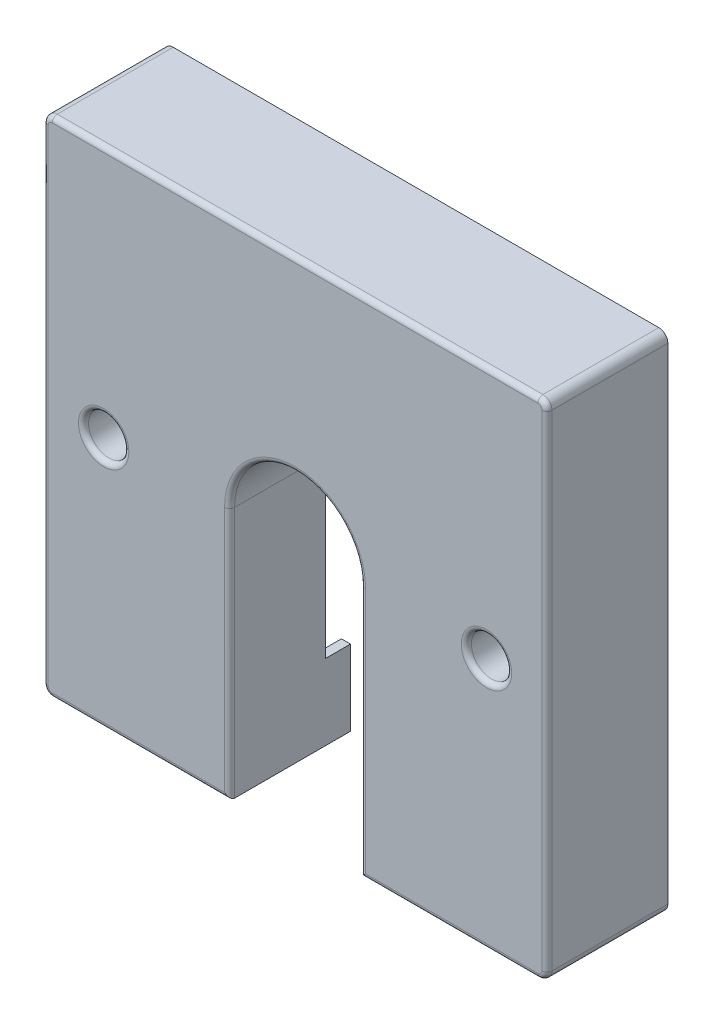
SolidWorks part; units mm, degrees
ref_plane "Front Plane" through (0, 0, 0) normal (0, 0, 1) x (1, 0, 0)
ref_plane "Top Plane" through (0, 0, 0) normal (0, 1, 0) x (1, 0, 0)
ref_plane "Right Plane" through (0, 0, 0) normal (1, 0, 0) x (0, 0, -1)
ref_plane "Plane1" through (0, 0, 121.3011) normal (0, 0, 1) x (1, 0, 0)
sketch "Sketch1" plane through (0, 0, 121.3011) normal (0, 0, 1) x (1, 0, 0)
  line L0 (-25.5449, 99.8167) -> (-25.5449, -0.1833)
  line L1 (-25.5449, -0.1833) -> (74.4551, -0.1833)
  line L2 (74.4551, -0.1833) -> (74.4551, 99.8167)
  line L3 (74.4551, 99.8167) -> (-25.5449, 99.8167)
  dimension "D1" = 100
  dimension "D2" = 100
extrude "Boss-Extrude1" add sketch "Sketch1" against normal blind 24
sketch "Sketch2" plane through (0, 0, 97.3011) normal (0, 0, -1) x (-1, 0, 0)
  line L0 (-37.4551, -0.1833) -> (-11.4551, -0.1833)
  line L1 (-11.4551, -0.1833) -> (-11.4551, 49.8167)
  line L2 (-37.4551, 49.8167) -> (-37.4551, -0.1833)
  line L3 (-74.4551, -0.1833) -> (-74.4551, 99.8167) construction
  line L5 (-74.4551, 99.8167) -> (25.5449, 99.8167) construction
  line L7 (25.5449, -0.1833) -> (-74.4551, -0.1833) construction
  arc A0 (-11.4551, 49.8167) -> (-37.4551, 49.8167) centre (-24.4551, 49.8167) ccw
  dimension "D1" = 13
  dimension "D3" = 50
  dimension "D4" = 0
  dimension "D2" = 50
extrude "Cut-Extrude1" cut sketch "Sketch2" against normal through all
sketch "Sketch3" plane through (0, 0, 97.3011) normal (0, 0, -1) x (-1, 0, 0)
  line L0 (-39.2551, 1.6167) -> (-39.2551, 49.6167)
  line L1 (-9.6551, 49.6167) -> (-9.6551, 1.6167)
  line L2 (-9.6551, 1.6167) -> (23.7449, 1.6167)
  line L3 (23.7449, 1.6167) -> (23.7449, 98.0167)
  line L4 (23.7449, 98.0167) -> (-72.6551, 98.0167)
  line L5 (-72.6551, 98.0167) -> (-72.6551, 1.6167)
  line L6 (-72.6551, 1.6167) -> (-39.2551, 1.6167)
  line L7 (-74.4551, -0.1833) -> (-74.4551, 99.8167) construction
  line L8 (-37.4551, 49.8167) -> (-37.4551, -0.1833) construction
  line L9 (-11.4551, -0.1833) -> (-11.4551, 49.8167) construction
  line L10 (25.5449, -0.1833) -> (-11.4551, -0.1833) construction
  line L11 (25.5449, 99.8167) -> (25.5449, -0.1833) construction
  line L12 (-74.4551, 99.8167) -> (25.5449, 99.8167) construction
  arc A0 (-39.2551, 49.6167) -> (-9.6551, 49.6167) centre (-24.4551, 49.6167) cw
  arc A1 (-11.4551, 49.8167) -> (-37.4551, 49.8167) centre (-24.4551, 49.8167) ccw construction
  dimension "D7" = 0.2
  dimension "D1" = 1.8
  dimension "D2" = 1.8
  dimension "D3" = 1.8
  dimension "D4" = 1.8
  dimension "D5" = 1.8
  dimension "D6" = 1.8
extrude "Cut-Extrude2" cut sketch "Sketch3" against normal blind 22
ref_plane "Plane2" through (0, 49.9426, 0) normal (0, -1, 0) x (1, 0, 0)
ref_plane "Plane3" through (0, 49.8167, 0) normal (0, -1, 0) x (-1, 0, 0)
sketch "Sketch4" plane through (0, 49.8167, 0) normal (0, -1, 0) x (1, 0, 0)
  line L0 (71.4551, 120.3011) -> (62.4551, 120.3011)
  line L1 (62.4551, 120.3011) -> (62.4551, 97.3011)
  line L2 (62.4551, 97.3011) -> (67.4551, 97.3011)
  line L3 (67.4551, 97.3011) -> (67.4551, 116.3011)
  line L4 (62.4551, 120.3011) -> (62.4551, 97.3011) construction
  line L5 (37.4551, 97.3011) -> (74.4551, 97.3011) construction
  line L7 (74.4551, 97.3011) -> (74.4551, 121.3011) construction
  arc A0 (67.4551, 116.3011) -> (71.4551, 120.3011) centre (71.4551, 116.3011) cw
  dimension "D1" = 0
  dimension "D2" = 7
  dimension "D3" = 5
revolve "Revolve1" add sketch "Sketch4" angle 360 about L4 reverse direction yes
sketch "Sketch5" plane through (0, 49.8167, 0) normal (0, -1, 0) x (1, 0, 0)
  line L0 (-4.5449, 120.3011) -> (-13.5449, 120.3011)
  line L1 (-13.5449, 120.3011) -> (-13.5449, 97.3011)
  line L2 (-13.5449, 97.3011) -> (-8.5449, 97.3011)
  line L3 (-8.5449, 97.3011) -> (-8.5449, 116.3011)
  line L4 (-13.5449, 120.3043) -> (-13.5449, 97.3011) construction
  line L5 (-25.5449, 97.3011) -> (11.4551, 97.3011) construction
  line L6 (-25.5449, 97.3011) -> (-25.5449, 121.3011) construction
  arc A0 (-8.5449, 116.3011) -> (-4.5449, 120.3011) centre (-4.5449, 116.3011) cw
  dimension "D1" = 0
  dimension "D2" = 12
revolve "Revolve2" add sketch "Sketch5" angle 360 about L4 reverse direction yes
hole_wizard "Hole1" positions "Sketch7" profile "Sketch6" legacy
sketch "Sketch7" plane through (0, 0, 121.3011) normal (0, 0, 1) x (1, 0, 0)
  line L0 (-25.5449, 99.8167) -> (-25.5449, -0.1833) construction
  line L1 (74.4551, -0.1833) -> (74.4551, 99.8167) construction
  line L2 (74.4551, 99.8167) -> (-25.5449, 99.8167) construction
  line L3 (37.4551, -0.1833) -> (74.4551, -0.1833) construction
  point P0 (-13.5449, 49.8167)
  point P1 (62.4551, 49.8167)
  dimension "D1" = 12
  dimension "D2" = 12
  dimension "D3" = 50
  dimension "D4" = 50
sketch "Sketch6" plane through (-13.5449, 49.8167, 121.3011) normal (1, 0, 0) x (0, -1, 0)
  line L0 (0, 0) -> (0, 40)
  line L1 (0, 40) -> (2, 40)
  line L2 (2, 40) -> (2, 20)
  line L3 (2, 20) -> (4, 20)
  line L4 (4, 20) -> (4, 0)
  line L5 (4, 0) -> (0, 0)
  line L6 (0, 110) -> (0, -10) construction
  dimension "Diameter" = 4
  dimension "Depth" = 40
  dimension "C-Bore Diameter" = 8
  dimension "C-Bore Depth" = 20
fillet "Fillet5" radius 1 10 edges at (72.6551, 49.8167, 119.3011) (24.4551, 98.0167, 119.3011) (-23.7449, 49.8167, 119.3011) (-7.0449, 1.6167, 119.3011) (9.6551, 25.6167, 119.3011) (24.4551, 64.4167, 119.3011) (39.2551, 25.6167, 119.3011) (55.9551, 1.6167, 119.3011) (56.1008, 49.8167, 119.3011) (-19.8992, 49.8167, 119.3011)
fillet "Fillet6" radius 1 10 edges at (24.4551, 62.8167, 121.3011) (11.4551, 24.8167, 121.3011) (-7.0449, -0.1833, 121.3011) (-25.5449, 49.8167, 121.3011) (24.4551, 99.8167, 121.3011) (74.4551, 49.8167, 121.3011) (55.9551, -0.1833, 121.3011) (37.4551, 24.8167, 121.3011) (66.4551, 49.8167, 121.3011) (-9.5449, 49.8167, 121.3011)
fillet "Fillet7" radius 1.8 8 edges at (74.1622, 0.1096, 121.0083) (74.1622, 99.5238, 121.0083) (-25.252, 99.5238, 121.0083) (-25.252, 0.1096, 121.0083) (-25.5449, -0.1833, 108.8011) (-25.5449, 99.8167, 108.8011) (74.4551, 99.8167, 108.8011) (74.4551, -0.1833, 108.8011)
sketch "Sketch10" plane through (0, 0, 97.3011) normal (0, 0, -1) x (-1, 0, 0)
  line L0 (-37.4551, -0.1833) -> (-72.6551, -0.1833) construction
  line L1 (-47.1983, 71.8743) -> (-0.7274, 71.8743)
  line L2 (-47.1983, 71.8743) -> (-47.1983, 14.8167)
  line L3 (-47.1983, 14.8167) -> (-0.7274, 14.8167)
  line L4 (-0.7274, 71.8743) -> (-0.7274, 14.8167)
  dimension "D1" = 15
extrude "Cut-Extrude4" cut sketch "Sketch10" against normal blind 5
fillet "Fillet8" radius 1 8 edges at (72.3622, 1.9096, 119.0083) (-23.452, 1.9096, 119.0083) (-23.452, 97.7238, 119.0083) (72.3622, 97.7238, 119.0083) (72.6551, 1.6167, 107.8011) (-23.7449, 1.6167, 107.8011) (-23.7449, 98.0167, 107.8011) (72.6551, 98.0167, 107.8011)
